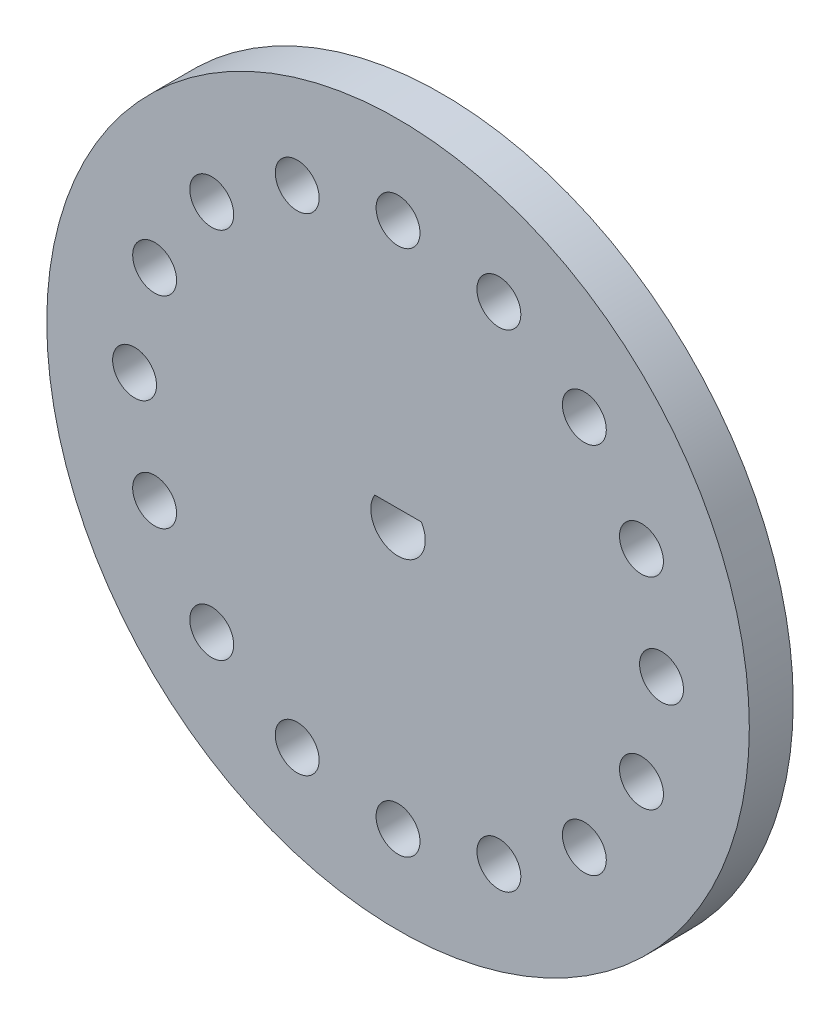
SolidWorks part; units mm, degrees
note: The reader was unsure of these and kept them because the rebuilt part matched: thickness of "Base-Flange1", "Sheet-Metal1", "Sheet-Metal2", "Sheet-Metal3".
material "6061 Alloy"
ref_plane "Front Plane" through (0, 0, 0) normal (0, 0, 1) x (1, 0, 0)
ref_plane "Top Plane" through (0, 0, 0) normal (0, 1, 0) x (1, 0, 0)
ref_plane "Right Plane" through (0, 0, 0) normal (1, 0, 0) x (0, 0, -1)
sketch "Sketch1" plane through (0, 0, 0) normal (0, 0, 1) x (1, 0, 0)
  line L0 (-3.5036, -3.1) -> (6.7306, -3.1) construction
  line L2 (2.6552, 1.6) -> (-2.6552, 1.6)
  circle A0 centre (0, 0) radius 40
  arc A1 (-2.6552, 1.6) -> (2.6552, 1.6) centre (0, 0) ccw
  dimension "D1" = 80
  dimension "D2" = 6.2
  dimension "D3" = 4.7
base flange "Base-Flange1" sketch "Sketch1" thickness 5 reverse thickness direction no parameters "D1"=0.7366
sketch "Sketch6" plane through (0, 0, 0) normal (0, 0, 1) x (1, 0, 0)
  circle A0 centre (0, 30) radius 2.5
  dimension "D1" = 5
  dimension "D2" = 30
extrude "Cut-Extrude1" cut sketch "Sketch6" against normal up to next normal cut yes
pattern_circular "CirPattern1" count 16 over 360 about axis through (0, 0, 0) along (0, 0, 1) of "Cut-Extrude1"
sketch "Bend-Lines1" [suppressed] plane through (0, 0, 0) normal (0, 1, 0) x (1, 0, 0)
sketch "Bounding-Box1" [suppressed] plane through (0, 0, 0) normal (0, 1, 0) x (1, 0, 0)
sheet metal parameters "Sheet-Metal1" thickness 5 parameters "D1"=0.7366
flat pattern "Flat-Pattern1" [suppressed]
sketch "Bend-Lines2" plane through (0, 0, 0) normal (0, 1, 0) x (1, 0, 0)
sketch3d "Bounding-Box2" [suppressed]
  line L0 (-39.9499, 40.05, 0) -> (-40.0499, -39.9499, 0) construction
  line L1 (40.05, 39.95, 0) -> (39.95, -40.0499, 0) construction
  line L2 (-39.9499, 40.05, 0) -> (40.05, 39.95, 0) construction
  line L3 (-40.0499, -39.9499, 0) -> (39.95, -40.0499, 0) construction
sheet metal parameters "Sheet-Metal2" thickness 5 parameters "D1"=0.7366, "D7"=0.7366
flat pattern "Flat-Pattern1"
sketch "Bend-Lines2" plane through (0, 0, 0) normal (0, 1, 0) x (1, 0, 0)
sketch3d "Bounding-Box2" [suppressed]
  line L0 (39.9499, 40.05, 0) -> (40.0499, -39.9499, 0) construction
  line L1 (-40.05, 39.95, 0) -> (-39.95, -40.0499, 0) construction
  line L2 (39.9499, 40.05, 0) -> (-40.05, 39.95, 0) construction
  line L3 (40.0499, -39.9499, 0) -> (-39.95, -40.0499, 0) construction
sheet metal parameters "Sheet-Metal3" thickness 5 parameters "D1"=0.7366, "D7"=0.7366
flat pattern "Flat-Pattern1"
sketch "Bend-Lines2" plane through (0, 0, 0) normal (0, 1, 0) x (1, 0, 0)
sketch3d "Bounding-Box2" [suppressed]
  line L0 (39.9499, 40.05, 0) -> (40.0499, -39.9499, 0) construction
  line L1 (-40.05, 39.95, 0) -> (-39.95, -40.0499, 0) construction
  line L2 (39.9499, 40.05, 0) -> (-40.05, 39.95, 0) construction
  line L3 (40.0499, -39.9499, 0) -> (-39.95, -40.0499, 0) construction
